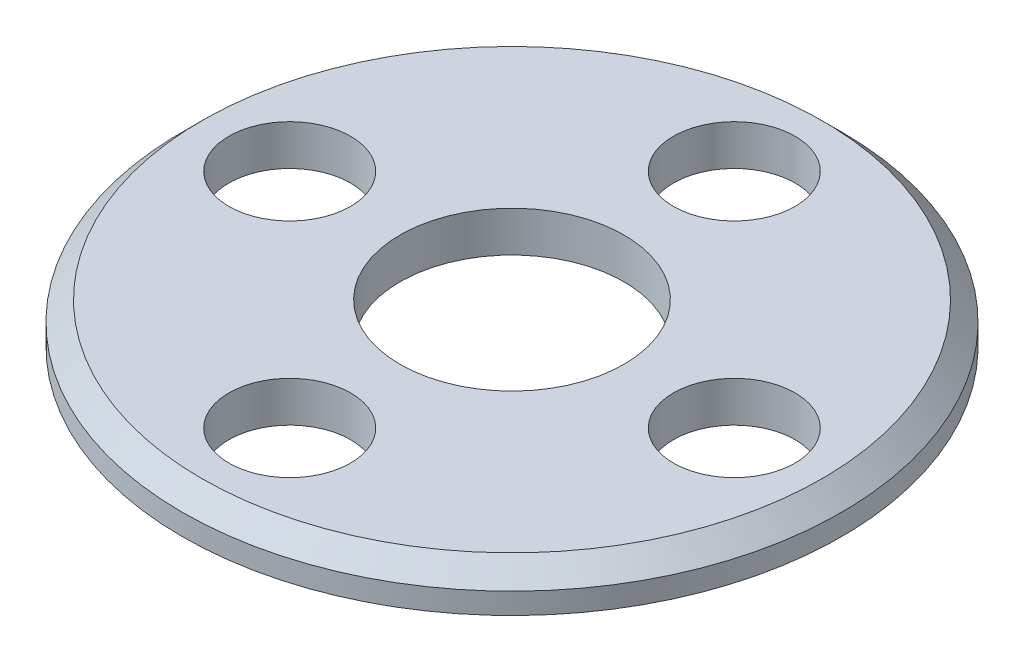
SolidWorks part; units mm, degrees
other "DetailItem2"
other "DetailItem3"
other "DetailItem4"
material "Alum Plate"
ref_plane "Front Plane" through (0, 0, 0) normal (0, 0, 1) x (1, 0, 0)
ref_plane "Top Plane" through (0, 0, 0) normal (0, 1, 0) x (1, 0, 0)
ref_plane "Right Plane" through (0, 0, 0) normal (1, 0, 0) x (0, 0, -1)
ref_axis "Centerline" through (0, 10.4775, 0) along (0, -1, 0)
sketch "Sketch1" plane through (0, 0, 0) normal (0, 1, 0) x (1, 0, 0)
  circle A0 centre (0, 0) radius 23.9697
  dimension "OuterDiameter" = 47.9394
extrude "ToothOD" add sketch "Sketch1" along normal mid plane 3.175
sketch "Sketch2" plane through (0, 1.5875, 0) normal (0, 1, 0) x (1, 0, 0)
  line L0 (0, 22.8013) -> (50000, 22.8013) construction
  line L1 (0, 23.9697) -> (50000, 23.9697) construction
  line L2 (0, 0) -> (0, 50000) construction
  arc A0 (-0.937, 23.5198) -> (0, 22.8013) centre (0, 23.7716) ccw
  arc A1 (-1.1386, 23.9426) -> (1.1386, 23.9426) centre (0, 0) cw
  circle A2 centre (0, 0) radius 23.9697 construction
  arc A3 (-0.937, 23.5198) -> (-1.0078, 23.7716) centre (-11.9754, 20.5533) ccw
  arc A4 (-1.0078, 23.7716) -> (-1.1386, 23.9426) centre (-1.2954, 23.6872) ccw
  circle A5 centre (0, 0) radius 23.9697 construction
  arc A6 (0.937, 23.5198) -> (1.0078, 23.7716) centre (11.9754, 20.5533) cw
  arc A7 (1.0078, 23.7716) -> (1.1386, 23.9426) centre (1.2954, 23.6872) cw
  arc A8 (0, 22.8013) -> (0.937, 23.5198) centre (0, 23.7716) ccw
  dimension "D1" = 1.9406
  dimension "D3" = 22.86
  dimension "D4" = 0.5994
  dimension "D2" = 1.1684
  dimension "D5" = 1.2954
extrude "ToothProfile" cut sketch "Sketch2" against normal through all
pattern_circular "ToothPattern" count 51 over 360 about axis through (0, 1.5875, 0) along (0, -1, 0) of "ToothProfile"
sketch "Sketch4" plane through (0, 0, 0) normal (0, 0, 1) x (1, 0, 0)
  line L0 (0, -5.08) -> (24.2237, -5.08)
  line L1 (0, -6.35) -> (25.7477, -6.35)
  line L2 (0, -6.35) -> (0, -5.08)
  line L3 (25.7477, -6.35) -> (25.7477, -5.842)
  line L4 (0, 0) -> (50000, 0) construction
  line L5 (25.7477, 6.35) -> (25.7477, 5.842)
  line L6 (0, 6.35) -> (0, 5.08)
  line L7 (0, 6.35) -> (25.7477, 6.35)
  line L8 (0, 5.08) -> (24.2237, 5.08)
  arc A0 (24.2237, -5.08) -> (24.6788, -5.1726) centre (23.944, -7.618) cw
  arc A2 (24.6788, -5.1726) -> (25.7477, -5.842) centre (23.5462, -8.1694) cw
  arc A3 (24.6788, 5.1726) -> (25.7477, 5.842) centre (23.5462, 8.1694) ccw
  arc A4 (24.2237, 5.08) -> (24.6788, 5.1726) centre (23.944, 7.618) ccw
  dimension "FlangeID" = 24.2237
  dimension "FlangeOD" = 25.7477
  dimension "D1" = 1.27
  dimension "D2" = 0.508
  dimension "D3" = 5.08
  dimension "D4" = 12.7
sketch "Sketch7" plane through (0, 0, 0) normal (0, -1, 0) x (1, 0, 0)
  line L1 (3.6662, 6.35) -> (-3.6662, 6.35)
  line L2 (-3.6662, 6.35) -> (-7.3323, 0)
  line L3 (-7.3323, 0) -> (-3.6662, -6.35)
  line L4 (-3.6662, -6.35) -> (3.6662, -6.35)
  line L5 (3.6662, -6.35) -> (7.3323, 0)
  line L6 (7.3323, 0) -> (3.6662, 6.35)
  circle A0 centre (0, 0) radius 6.35 construction
  dimension "HexBoreDi," = 12.7
extrude "Bore" [suppressed] cut sketch "Sketch7" against normal through all both and the other way through all
sketch "Sketch13" plane through (0, 1.5875, 0) normal (0, 1, 0) x (1, 0, 0)
  line L0 (-3.81, 20.2565) -> (3.81, 20.2565) construction
  line L4 (0, 20.2565) -> (0, 17.399) construction
  arc A0 (-3.81, 20.2565) -> (3.81, 20.2565) centre (0, 17.399) ccw
  circle A1 centre (0, 0) radius 8.7694
  arc A2 (3.81, 20.2565) -> (-3.81, 20.2565) centre (0, 17.399) ccw
  dimension "D1" = 9.525
  dimension "D3" = 17.5387
  dimension "D2" = 17.399
  dimension "D4" = 7.62
extrude "Cut-Extrude2" cut sketch "Sketch13" against normal through all
pattern_circular "CirPattern1" count 4 over 360 about axis through (0, -1.5875, 0) along (0, 1, 0) of "Cut-Extrude2"
sketch "Sketch14" plane through (0, 1.5875, 0) normal (0, 1, 0) x (1, 0, 0)
  circle A0 centre (0, 0) radius 22.733
  circle A1 centre (0, 0) radius 23.9697
  arc A3 (-3.2802, -23.7442) -> (-2.6104, -23.8271) centre (0, 0) ccw construction
  dimension "D1" = 45.466
extrude "Cut-Extrude3" [suppressed] cut sketch "Sketch14" against normal through all
sketch "Sketch15" plane through (0, 1.5875, 0) normal (0, 1, 0) x (1, 0, 0)
  circle A0 centre (0, 0) radius 25.7969
  arc A306 (6.9442, 22.9418) -> (6.7756, 22.8078) centre (7.0339, 22.6558) ccw
  arc A307 (6.7756, 22.8078) -> (6.6455, 22.5808) centre (16.6269, 17.0116) ccw
  arc A308 (4.8281, 23.038) -> (6.6455, 22.5808) centre (5.7982, 23.0536) ccw
  arc A309 (4.8281, 23.038) -> (4.8208, 23.2994) centre (-6.6004, 22.8535) ccw
  arc A310 (4.8208, 23.2994) -> (4.7357, 23.4972) centre (4.5214, 23.2877) ccw
  arc A311 (4.7357, 23.4972) -> (4.0723, 23.6213) centre (0, 0) ccw
  arc A312 (4.0723, 23.6213) -> (3.9214, 23.4676) centre (4.1965, 23.3485) ccw
  arc A313 (3.9214, 23.4676) -> (3.8202, 23.2264) centre (14.4104, 18.9259) ccw
  arc A314 (1.9604, 23.4567) -> (3.8202, 23.2264) centre (2.9212, 23.5914) ccw
  arc A315 (1.9604, 23.4567) -> (1.9211, 23.7153) centre (-9.3589, 21.8692) ccw
  arc A316 (1.9211, 23.7153) -> (1.8123, 23.9011) centre (1.6253, 23.6668) ccw
  arc A317 (1.8123, 23.9011) -> (1.1386, 23.9426) centre (0, 0) ccw
  arc A318 (1.1386, 23.9426) -> (1.0078, 23.7716) centre (1.2954, 23.6872) ccw
  arc A319 (1.0078, 23.7716) -> (0.937, 23.5198) centre (11.9754, 20.5533) ccw
  arc A320 (-0.937, 23.5198) -> (0.937, 23.5198) centre (0, 23.7716) ccw
  arc A321 (-0.937, 23.5198) -> (-1.0078, 23.7716) centre (-11.9754, 20.5533) ccw
  arc A322 (-1.0078, 23.7716) -> (-1.1386, 23.9426) centre (-1.2954, 23.6872) ccw
  arc A323 (-1.1386, 23.9426) -> (-1.8123, 23.9011) centre (0, 0) ccw
  arc A324 (-1.8123, 23.9011) -> (-1.9211, 23.7153) centre (-1.6253, 23.6668) ccw
  arc A325 (-1.9211, 23.7153) -> (-1.9604, 23.4567) centre (9.3589, 21.8692) ccw
  arc A326 (-3.8202, 23.2264) -> (-1.9604, 23.4567) centre (-2.9212, 23.5914) ccw
  arc A327 (-3.8202, 23.2264) -> (-3.9214, 23.4676) centre (-14.4104, 18.9259) ccw
  arc A328 (-3.9214, 23.4676) -> (-4.0723, 23.6213) centre (-4.1965, 23.3485) ccw
  arc A329 (-4.0723, 23.6213) -> (-4.7357, 23.4972) centre (0, 0) ccw
  arc A330 (-4.7357, 23.4972) -> (-4.8208, 23.2994) centre (-4.5214, 23.2877) ccw
  arc A331 (-4.8208, 23.2994) -> (-4.8281, 23.038) centre (6.6004, 22.8535) ccw
  arc A332 (-6.6455, 22.5808) -> (-4.8281, 23.038) centre (-5.7982, 23.0536) ccw
  arc A333 (-6.6455, 22.5808) -> (-6.7756, 22.8078) centre (-16.6269, 17.0116) ccw
  arc A334 (-6.7756, 22.8078) -> (-6.9442, 22.9418) centre (-7.0339, 22.6558) ccw
  arc A335 (-6.9442, 22.9418) -> (-7.5873, 22.7372) centre (0, 0) ccw
  arc A336 (-7.5873, 22.7372) -> (-7.6475, 22.5304) centre (-7.3489, 22.5556) ccw
  arc A337 (-7.6475, 22.5304) -> (-7.6226, 22.27) centre (3.742, 23.4914) ccw
  arc A338 (-9.3701, 21.593) -> (-7.6226, 22.27) centre (-8.5873, 22.1663) ccw
  arc A339 (-9.3701, 21.593) -> (-9.527, 21.8023) centre (-18.5914, 14.8394) ccw
  arc A340 (-9.527, 21.8023) -> (-9.7108, 21.9145) centre (-9.7647, 21.6197) ccw
  arc A341 (-9.7108, 21.9145) -> (-10.324, 21.6324) centre (0, 0) ccw
  arc A342 (-10.324, 21.6324) -> (-10.3583, 21.4198) centre (-10.065, 21.4816) ccw
  arc A343 (-10.3583, 21.4198) -> (-10.3015, 21.1645) centre (0.8268, 23.7732) ccw
  arc A344 (-11.9526, 20.2779) -> (-10.3015, 21.1645) centre (-11.2462, 20.9431) ccw
  arc A345 (-11.9526, 20.2779) -> (-12.1341, 20.4663) centre (-20.2741, 12.4423) ccw
  arc A346 (-12.1341, 20.4663) -> (-12.3303, 20.5551) centre (-12.3475, 20.2559) ccw
  arc A347 (-12.3303, 20.5551) -> (-12.9041, 20.1998) centre (0, 0) ccw
  arc A348 (-12.9041, 20.1998) -> (-12.912, 19.9846) centre (-12.6285, 20.0819) ccw
  arc A349 (-12.912, 19.9846) -> (-12.8243, 19.7382) centre (-2.1009, 23.6946) ccw
  arc A350 (-14.3539, 18.6554) -> (-12.8243, 19.7382) centre (-13.7346, 19.4023) ccw
  arc A351 (-14.3539, 18.6554) -> (-14.5572, 18.82) centre (-21.6494, 9.8565) ccw
  arc A352 (-14.5572, 18.82) -> (-14.7628, 18.884) centre (-14.7431, 18.585) ccw
  arc A353 (-14.7628, 18.884) -> (-15.2886, 18.4609) centre (0, 0) ccw
  arc A354 (-15.2886, 18.4609) -> (-15.27, 18.2464) centre (-15.0006, 18.3778) ccw
  arc A355 (-15.27, 18.2464) -> (-15.1527, 18.0126) centre (-4.9968, 23.2569) ccw
  arc A356 (-16.5376, 16.75) -> (-15.1527, 18.0126) centre (-16.0148, 17.5674) ccw
  arc A357 (-16.5376, 16.75) -> (-16.7596, 16.8885) centre (-22.6966, 7.1213) ccw
  arc A358 (-16.7596, 16.8885) -> (-16.9715, 16.9267) centre (-16.9153, 16.6323) ccw
  arc A359 (-16.9715, 16.9267) -> (-17.4414, 16.4422) centre (0, 0) ccw
  arc A360 (-17.4414, 16.4422) -> (-17.3966, 16.2316) centre (-17.1454, 16.3951) ccw
  arc A361 (-17.3966, 16.2316) -> (-17.2514, 16.014) centre (-7.8169, 22.4665) ccw
  arc A362 (-18.4707, 14.5908) -> (-17.2514, 16.014) centre (-18.0523, 15.4662) ccw
  arc A363 (-18.4707, 14.5908) -> (-18.708, 14.7009) centre (-23.3997, 4.2782) ccw
  arc A364 (-18.708, 14.7009) -> (-18.923, 14.7128) centre (-18.831, 14.4276) ccw
  arc A365 (-18.923, 14.7128) -> (-19.3297, 14.1742) centre (0, 0) ccw
  arc A366 (-19.3297, 14.1742) -> (-19.2594, 13.9707) centre (-19.0302, 14.1638) ccw
  arc A367 (-19.2594, 13.9707) -> (-19.0886, 13.7726) centre (-10.5185, 21.3356) ccw
  arc A368 (-20.1237, 12.2104) -> (-19.0886, 13.7726) centre (-19.8161, 13.1306) ccw
  arc A369 (-20.1237, 12.2104) -> (-20.3727, 12.2905) centre (-23.7481, 1.3702) ccw
  arc A370 (-20.3727, 12.2905) -> (-20.5876, 12.2759) centre (-20.4612, 12.0041) ccw
  arc A371 (-20.5876, 12.2759) -> (-20.925, 11.6914) centre (0, 0) ccw
  arc A372 (-20.925, 11.6914) -> (-20.8302, 11.4981) centre (-20.6265, 11.7179) ccw
  arc A373 (-20.8302, 11.4981) -> (-20.6364, 11.3225) centre (-13.0607, 19.8813) ccw
  arc A374 (-21.4717, 9.6449) -> (-20.6364, 11.3225) centre (-21.2795, 10.5959) ccw
  arc A375 (-21.4717, 9.6449) -> (-21.7287, 9.6938) centre (-23.7365, -1.5585) ccw
  arc A376 (-21.7287, 9.6938) -> (-21.9401, 9.6529) centre (-21.7813, 9.3987) ccw
  arc A377 (-21.9401, 9.6529) -> (-22.2032, 9.0314) centre (0, 0) ccw
  arc A378 (-22.2032, 9.0314) -> (-22.0853, 8.8511) centre (-21.9102, 9.0943) ccw
  arc A379 (-22.0853, 8.8511) -> (-21.8713, 8.7007) centre (-15.4049, 18.1256) ccw
  arc A380 (-22.4942, 6.9331) -> (-21.8713, 8.7007) centre (-22.4203, 7.9006) ccw
  arc A381 (-22.4942, 6.9331) -> (-22.7552, 6.9501) centre (-23.365, -4.4636) ccw
  arc A382 (-22.7552, 6.9501) -> (-22.96, 6.8836) centre (-22.7712, 6.6508) ccw
  arc A383 (-22.96, 6.8836) -> (-23.1447, 6.2344) centre (0, 0) ccw
  arc A384 (-23.1447, 6.2344) -> (-23.0056, 6.07) centre (-22.8617, 6.3329) ccw
  arc A385 (-23.0056, 6.07) -> (-22.7748, 5.947) centre (-17.5156, 16.0952) ccw
  arc A386 (-23.1757, 4.1163) -> (-22.7748, 5.947) centre (-23.2212, 5.0855) ccw
  arc A387 (-23.1757, 4.1163) -> (-23.4368, 4.1011) centre (-22.6394, -7.3011) ccw
  arc A388 (-23.4368, 4.1011) -> (-23.6319, 4.0099) centre (-23.4159, 3.8021) ccw
  arc A389 (-23.6319, 4.0099) -> (-23.7355, 3.3429) centre (0, 0) ccw
  arc A390 (-23.7355, 3.3429) -> (-23.5772, 3.1969) centre (-23.4666, 3.4755) ccw
  arc A391 (-23.5772, 3.1969) -> (-23.333, 3.1032) centre (-19.3607, 13.8207) ccw
  arc A392 (-23.5059, 1.2371) -> (-23.333, 3.1032) centre (-23.6702, 2.1934) ccw
  arc A393 (-23.5059, 1.2371) -> (-23.7632, 1.1899) centre (-21.5706, -10.0279) ccw
  arc A394 (-23.7632, 1.1899) -> (-23.9456, 1.0754) centre (-23.7057, 0.8957) ccw
  arc A395 (-23.9456, 1.0754) -> (-23.9664, 0.4008) centre (0, 0) ccw
  arc A396 (-23.9664, 0.4008) -> (-23.7913, 0.2753) centre (-23.7159, 0.5653) ccw
  arc A397 (-23.7913, 0.2753) -> (-23.5375, 0.2123) centre (-20.9124, 11.3368) ccw
  arc A398 (-23.4798, -1.6609) -> (-23.5375, 0.2123) centre (-23.7603, -0.732) ccw
  arc A399 (-23.4798, -1.6609) -> (-23.7293, -1.7394) centre (-20.1748, -12.6026) ccw
  arc A400 (-23.7293, -1.7394) -> (-23.8962, -1.8754) centre (-23.6361, -2.0242) ccw
  arc A401 (-23.8962, -1.8754) -> (-23.834, -2.5474) centre (0, 0) ccw
  arc A402 (-23.834, -2.5474) -> (-23.6449, -2.6505) centre (-23.6056, -2.3533) ccw
  arc A403 (-23.6449, -2.6505) -> (-23.3852, -2.6818) centre (-22.147, 8.6809) ccw
  arc A404 (-23.0977, -4.5337) -> (-23.3852, -2.6818) centre (-23.4903, -3.6464) ccw
  arc A405 (-23.0977, -4.5337) -> (-23.3357, -4.6422) centre (-18.4732, -14.9864) ccw
  arc A406 (-23.3357, -4.6422) -> (-23.4846, -4.7978) centre (-23.2082, -4.9135) ccw
  arc A407 (-23.4846, -4.7978) -> (-23.3403, -5.4571) centre (0, 0) ccw
  arc A408 (-23.3403, -5.4571) -> (-23.1399, -5.5361) centre (-23.1375, -5.2364) ccw
  arc A409 (-23.1399, -5.5361) -> (-22.8783, -5.5352) centre (-23.0459, 5.8935) ccw
  arc A410 (-22.3655, -7.3378) -> (-22.8783, -5.5352) centre (-22.8641, -6.5054) ccw
  arc A411 (-22.3655, -7.3378) -> (-22.5883, -7.4747) centre (-16.4915, -17.1429) ccw
  arc A412 (-22.5883, -7.4747) -> (-22.7171, -7.6474) centre (-22.4285, -7.7283) ccw
  arc A413 (-22.7171, -7.6474) -> (-22.4927, -8.2839) centre (0, 0) ccw
  arc A414 (-22.4927, -8.2839) -> (-22.2842, -8.3377) centre (-22.3186, -8.04) ccw
  arc A415 (-22.2842, -8.3377) -> (-22.0247, -8.3048) centre (-23.5955, 3.0168) ccw
  arc A416 (-21.2942, -10.0306) -> (-22.0247, -8.3048) centre (-21.8914, -9.2658) ccw
  arc A417 (-21.2942, -10.0306) -> (-21.4986, -10.1939) centre (-14.2598, -19.0396) ccw
  arc A418 (-21.4986, -10.1939) -> (-21.6051, -10.3811) centre (-21.3087, -10.4259) ccw
  arc A419 (-21.6051, -10.3811) -> (-21.3043, -10.9852) centre (0, 0) ccw
  arc A420 (-21.3043, -10.9852) -> (-21.0907, -11.013) centre (-21.1614, -10.7217) ccw
  arc A421 (-21.0907, -11.013) -> (-20.8372, -10.9484) centre (-23.7874, 0.0943) ccw
  arc A422 (-19.9002, -12.5714) -> (-20.8372, -10.9484) centre (-20.5868, -11.8858) ccw
  arc A423 (-19.9002, -12.5714) -> (-20.0829, -12.7586) centre (-11.812, -20.6476) ccw
  arc A424 (-20.0829, -12.7586) -> (-20.1656, -12.9574) centre (-19.866, -12.9654) ccw
  arc A425 (-20.1656, -12.9574) -> (-19.7928, -13.52) centre (0, 0) ccw
  arc A426 (-19.7928, -13.52) -> (-19.5775, -13.5213) centre (-19.6834, -13.241) ccw
  arc A427 (-19.5775, -13.5213) -> (-19.3339, -13.4261) centre (-23.6187, -2.8296) ccw
  arc A428 (-18.2045, -14.9216) -> (-19.3339, -13.4261) centre (-18.9701, -14.3256) ccw
  arc A429 (-18.2045, -14.9216) -> (-18.3628, -15.1298) centre (-9.1851, -21.9427) ccw
  arc A430 (-18.3628, -15.1298) -> (-18.4205, -15.3373) centre (-18.1221, -15.3085) ccw
  arc A431 (-18.4205, -15.3373) -> (-17.9814, -15.8499) centre (0, 0) ccw
  arc A432 (-17.9814, -15.8499) -> (-17.7675, -15.8247) centre (-17.9071, -15.5595) ccw
  arc A433 (-17.7675, -15.8247) -> (-17.5374, -15.7002) centre (-23.0919, -5.7106) ccw
  arc A434 (-16.2328, -17.0456) -> (-17.5374, -15.7002) centre (-17.0659, -16.5482) ccw
  arc A435 (-16.2328, -17.0456) -> (-16.3643, -17.2717) centre (-6.419, -22.9051) ccw
  arc A436 (-16.3643, -17.2717) -> (-16.3961, -17.4847) centre (-16.1035, -17.4194) ccw
  arc A437 (-16.3961, -17.4847) -> (-15.8973, -17.9394) centre (0, 0) ccw
  arc A438 (-15.8973, -17.9394) -> (-15.6881, -17.8882) centre (-15.8593, -17.6421) ccw
  arc A439 (-15.6881, -17.8882) -> (-15.4751, -17.7363) centre (-22.2152, -8.505) ccw
  arc A440 (-14.0151, -18.9112) -> (-15.4751, -17.7363) centre (-14.903, -18.52) ccw
  arc A441 (-14.0151, -18.9112) -> (-14.1178, -19.1518) centre (-3.5556, -23.5203) ccw
  arc A442 (-14.1178, -19.1518) -> (-14.1231, -19.3671) centre (-13.8408, -19.2664) ccw
  arc A443 (-14.1231, -19.3671) -> (-13.5723, -19.757) centre (0, 0) ccw
  arc A444 (-13.5723, -19.757) -> (-13.371, -19.6805) centre (-13.5711, -19.4573) ccw
  arc A445 (-13.371, -19.6805) -> (-13.1782, -19.5036) centre (-21.0016, -11.1706) ccw
  arc A446 (-11.5849, -20.4902) -> (-13.1782, -19.5036) centre (-12.5141, -20.211) ccw
  arc A447 (-11.5849, -20.4902) -> (-11.6573, -20.7416) centre (-0.6383, -23.779) ccw
  arc A448 (-11.6573, -20.7416) -> (-11.6361, -20.9559) centre (-11.3683, -20.8212) ccw
  arc A449 (-11.6361, -20.9559) -> (-11.0415, -21.2752) centre (0, 0) ccw
  arc A450 (-11.0415, -21.2752) -> (-10.8511, -21.1744) centre (-11.0771, -20.9776) ccw
  arc A451 (-10.8511, -21.1744) -> (-10.6816, -20.9753) centre (-19.4697, -13.6667) ccw
  arc A452 (-8.9791, -21.7585) -> (-10.6816, -20.9753) centre (-9.9356, -21.5957) ccw
  arc A453 (-8.9791, -21.7585) -> (-9.02, -22.0169) centre (2.2887, -23.6772) ccw
  arc A454 (-9.02, -22.0169) -> (-8.9727, -22.227) centre (-8.7235, -22.0604) ccw
  arc A455 (-8.9727, -22.227) -> (-8.3433, -22.4708) centre (0, 0) ccw
  arc A456 (-8.3433, -22.4708) -> (-8.1668, -22.3474) centre (-8.4153, -22.1798) ccw
  arc A457 (-8.1668, -22.3474) -> (-8.023, -22.1289) centre (-17.6426, -15.9558) ccw
  arc A458 (-6.2371, -22.697) -> (-8.023, -22.1289) centre (-7.2064, -22.6529) ccw
  arc A459 (-6.2371, -22.697) -> (-6.246, -22.9585) centre (5.181, -23.2165) ccw
  arc A460 (-6.246, -22.9585) -> (-6.1732, -23.1611) centre (-5.9464, -22.9652) ccw
  arc A461 (-6.1732, -23.1611) -> (-5.5187, -23.3258) centre (0, 0) ccw
  arc A462 (-5.5187, -23.3258) -> (-5.3587, -23.1816) centre (-5.6259, -23.0458) ccw
  arc A463 (-5.3587, -23.1816) -> (-5.2428, -22.9471) centre (-15.5481, -18.0029) ccw
  arc A464 (-3.4007, -23.2915) -> (-5.2428, -22.9471) centre (-4.368, -23.3668) ccw
  arc A465 (-3.4007, -23.2915) -> (-3.3774, -23.552) centre (7.9948, -22.4038) ccw
  arc A466 (-3.3774, -23.552) -> (-3.2802, -23.7442) centre (-3.0792, -23.5219) ccw
  arc A467 (-3.2802, -23.7442) -> (-2.6104, -23.8271) centre (0, 0) ccw
  arc A468 (-2.6104, -23.8271) -> (-2.4693, -23.6645) centre (-2.7511, -23.5625) ccw
  arc A469 (-2.4693, -23.6645) -> (-2.3832, -23.4175) centre (-13.2179, -19.7771) ccw
  arc A470 (-0.5126, -23.5328) -> (-2.3832, -23.4175) centre (-1.4634, -23.7265) ccw
  arc A471 (-0.5126, -23.5328) -> (-0.4575, -23.7885) centre (10.6874, -21.2516) ccw
  arc A472 (-0.4575, -23.7885) -> (-0.3375, -23.9673) centre (-0.1653, -23.722) ccw
  arc A473 (-0.3375, -23.9673) -> (0.3375, -23.9673) centre (0, 0) ccw
  arc A474 (0.3375, -23.9673) -> (0.4575, -23.7885) centre (0.1653, -23.722) ccw
  arc A475 (0.4575, -23.7885) -> (0.5126, -23.5328) centre (-10.6874, -21.2516) ccw
  arc A476 (2.3832, -23.4175) -> (0.5126, -23.5328) centre (1.4634, -23.7265) ccw
  arc A477 (2.3832, -23.4175) -> (2.4693, -23.6645) centre (13.2179, -19.7771) ccw
  arc A478 (2.4693, -23.6645) -> (2.6104, -23.8271) centre (2.7511, -23.5625) ccw
  arc A479 (2.6104, -23.8271) -> (3.2802, -23.7442) centre (0, 0) ccw
  arc A480 (3.2802, -23.7442) -> (3.3774, -23.552) centre (3.0792, -23.5219) ccw
  arc A481 (3.3774, -23.552) -> (3.4007, -23.2915) centre (-7.9948, -22.4038) ccw
  arc A482 (5.2428, -22.9471) -> (3.4007, -23.2915) centre (4.368, -23.3668) ccw
  arc A483 (5.2428, -22.9471) -> (5.3587, -23.1816) centre (15.5481, -18.0029) ccw
  arc A484 (5.3587, -23.1816) -> (5.5187, -23.3258) centre (5.6259, -23.0458) ccw
  arc A485 (5.5187, -23.3258) -> (6.1732, -23.1611) centre (0, 0) ccw
  arc A486 (6.1732, -23.1611) -> (6.246, -22.9585) centre (5.9464, -22.9652) ccw
  arc A487 (6.246, -22.9585) -> (6.2371, -22.697) centre (-5.181, -23.2165) ccw
  arc A488 (8.023, -22.1289) -> (6.2371, -22.697) centre (7.2064, -22.6529) ccw
  arc A489 (8.023, -22.1289) -> (8.1668, -22.3474) centre (17.6426, -15.9558) ccw
  arc A490 (8.1668, -22.3474) -> (8.3433, -22.4708) centre (8.4153, -22.1798) ccw
  arc A491 (8.3433, -22.4708) -> (8.9727, -22.227) centre (0, 0) ccw
  arc A492 (8.9727, -22.227) -> (9.02, -22.0169) centre (8.7235, -22.0604) ccw
  arc A493 (9.02, -22.0169) -> (8.9791, -21.7585) centre (-2.2887, -23.6772) ccw
  arc A494 (10.6816, -20.9753) -> (8.9791, -21.7585) centre (9.9356, -21.5957) ccw
  arc A495 (10.6816, -20.9753) -> (10.8511, -21.1744) centre (19.4697, -13.6667) ccw
  arc A496 (10.8511, -21.1744) -> (11.0415, -21.2752) centre (11.0771, -20.9776) ccw
  arc A497 (11.0415, -21.2752) -> (11.6361, -20.9559) centre (0, 0) ccw
  arc A498 (11.6361, -20.9559) -> (11.6573, -20.7416) centre (11.3683, -20.8212) ccw
  arc A499 (11.6573, -20.7416) -> (11.5849, -20.4902) centre (0.6383, -23.779) ccw
  arc A500 (13.1782, -19.5036) -> (11.5849, -20.4902) centre (12.5141, -20.211) ccw
  arc A501 (13.1782, -19.5036) -> (13.371, -19.6805) centre (21.0016, -11.1706) ccw
  arc A502 (13.371, -19.6805) -> (13.5723, -19.757) centre (13.5711, -19.4573) ccw
  arc A503 (13.5723, -19.757) -> (14.1231, -19.3671) centre (0, 0) ccw
  arc A504 (14.1231, -19.3671) -> (14.1178, -19.1518) centre (13.8408, -19.2664) ccw
  arc A505 (14.1178, -19.1518) -> (14.0151, -18.9112) centre (3.5556, -23.5203) ccw
  arc A506 (15.4751, -17.7363) -> (14.0151, -18.9112) centre (14.903, -18.52) ccw
  arc A507 (15.4751, -17.7363) -> (15.6881, -17.8882) centre (22.2152, -8.505) ccw
  arc A508 (15.6881, -17.8882) -> (15.8973, -17.9394) centre (15.8593, -17.6421) ccw
  arc A509 (15.8973, -17.9394) -> (16.3961, -17.4847) centre (0, 0) ccw
  arc A510 (16.3961, -17.4847) -> (16.3643, -17.2717) centre (16.1035, -17.4194) ccw
  arc A511 (16.3643, -17.2717) -> (16.2328, -17.0456) centre (6.419, -22.9051) ccw
  arc A512 (17.5374, -15.7002) -> (16.2328, -17.0456) centre (17.0659, -16.5482) ccw
  arc A513 (17.5374, -15.7002) -> (17.7675, -15.8247) centre (23.0919, -5.7106) ccw
  arc A514 (17.7675, -15.8247) -> (17.9814, -15.8499) centre (17.9071, -15.5595) ccw
  arc A515 (17.9814, -15.8499) -> (18.4205, -15.3373) centre (0, 0) ccw
  arc A516 (18.4205, -15.3373) -> (18.3628, -15.1298) centre (18.1221, -15.3085) ccw
  arc A517 (18.3628, -15.1298) -> (18.2045, -14.9216) centre (9.1851, -21.9427) ccw
  arc A518 (19.3339, -13.4261) -> (18.2045, -14.9216) centre (18.9701, -14.3256) ccw
  arc A519 (19.3339, -13.4261) -> (19.5775, -13.5213) centre (23.6187, -2.8296) ccw
  arc A520 (19.5775, -13.5213) -> (19.7928, -13.52) centre (19.6834, -13.241) ccw
  arc A521 (19.7928, -13.52) -> (20.1656, -12.9574) centre (0, 0) ccw
  arc A522 (20.1656, -12.9574) -> (20.0829, -12.7586) centre (19.866, -12.9654) ccw
  arc A523 (20.0829, -12.7586) -> (19.9002, -12.5714) centre (11.812, -20.6476) ccw
  arc A524 (20.8372, -10.9484) -> (19.9002, -12.5714) centre (20.5868, -11.8858) ccw
  arc A525 (20.8372, -10.9484) -> (21.0907, -11.013) centre (23.7874, 0.0943) ccw
  arc A526 (21.0907, -11.013) -> (21.3043, -10.9852) centre (21.1614, -10.7217) ccw
  arc A527 (21.3043, -10.9852) -> (21.6051, -10.3811) centre (0, 0) ccw
  arc A528 (21.6051, -10.3811) -> (21.4986, -10.1939) centre (21.3087, -10.4259) ccw
  arc A529 (21.4986, -10.1939) -> (21.2942, -10.0306) centre (14.2598, -19.0396) ccw
  arc A530 (22.0247, -8.3048) -> (21.2942, -10.0306) centre (21.8914, -9.2658) ccw
  arc A531 (22.0247, -8.3048) -> (22.2842, -8.3377) centre (23.5955, 3.0168) ccw
  arc A532 (22.2842, -8.3377) -> (22.4927, -8.2839) centre (22.3186, -8.04) ccw
  arc A533 (22.4927, -8.2839) -> (22.7171, -7.6474) centre (0, 0) ccw
  arc A534 (22.7171, -7.6474) -> (22.5883, -7.4747) centre (22.4285, -7.7283) ccw
  arc A535 (22.5883, -7.4747) -> (22.3655, -7.3378) centre (16.4915, -17.1429) ccw
  arc A536 (22.8783, -5.5352) -> (22.3655, -7.3378) centre (22.8641, -6.5054) ccw
  arc A537 (22.8783, -5.5352) -> (23.1399, -5.5361) centre (23.0459, 5.8935) ccw
  arc A538 (23.1399, -5.5361) -> (23.3403, -5.4571) centre (23.1375, -5.2364) ccw
  arc A539 (23.3403, -5.4571) -> (23.4846, -4.7978) centre (0, 0) ccw
  arc A540 (23.4846, -4.7978) -> (23.3357, -4.6422) centre (23.2082, -4.9135) ccw
  arc A541 (23.3357, -4.6422) -> (23.0977, -4.5337) centre (18.4732, -14.9864) ccw
  arc A542 (23.3852, -2.6818) -> (23.0977, -4.5337) centre (23.4903, -3.6464) ccw
  arc A543 (23.3852, -2.6818) -> (23.6449, -2.6505) centre (22.147, 8.6809) ccw
  arc A544 (23.6449, -2.6505) -> (23.834, -2.5474) centre (23.6056, -2.3533) ccw
  arc A545 (23.834, -2.5474) -> (23.8962, -1.8754) centre (0, 0) ccw
  arc A546 (23.8962, -1.8754) -> (23.7293, -1.7394) centre (23.6361, -2.0242) ccw
  arc A547 (23.7293, -1.7394) -> (23.4798, -1.6609) centre (20.1748, -12.6026) ccw
  arc A548 (23.5375, 0.2123) -> (23.4798, -1.6609) centre (23.7603, -0.732) ccw
  arc A549 (23.5375, 0.2123) -> (23.7913, 0.2753) centre (20.9124, 11.3368) ccw
  arc A550 (23.7913, 0.2753) -> (23.9664, 0.4008) centre (23.7159, 0.5653) ccw
  arc A551 (23.9664, 0.4008) -> (23.9456, 1.0754) centre (0, 0) ccw
  arc A552 (23.9456, 1.0754) -> (23.7632, 1.1899) centre (23.7057, 0.8957) ccw
  arc A553 (23.7632, 1.1899) -> (23.5059, 1.2371) centre (21.5706, -10.0279) ccw
  arc A554 (23.333, 3.1032) -> (23.5059, 1.2371) centre (23.6702, 2.1934) ccw
  arc A555 (23.333, 3.1032) -> (23.5772, 3.1969) centre (19.3607, 13.8207) ccw
  arc A556 (23.5772, 3.1969) -> (23.7355, 3.3429) centre (23.4666, 3.4755) ccw
  arc A557 (23.7355, 3.3429) -> (23.6319, 4.0099) centre (0, 0) ccw
  arc A558 (23.6319, 4.0099) -> (23.4368, 4.1011) centre (23.4159, 3.8021) ccw
  arc A559 (23.4368, 4.1011) -> (23.1757, 4.1163) centre (22.6394, -7.3011) ccw
  arc A560 (22.7748, 5.947) -> (23.1757, 4.1163) centre (23.2212, 5.0855) ccw
  arc A561 (22.7748, 5.947) -> (23.0056, 6.07) centre (17.5156, 16.0952) ccw
  arc A562 (23.0056, 6.07) -> (23.1447, 6.2344) centre (22.8617, 6.3329) ccw
  arc A563 (23.1447, 6.2344) -> (22.96, 6.8836) centre (0, 0) ccw
  arc A564 (22.96, 6.8836) -> (22.7552, 6.9501) centre (22.7712, 6.6508) ccw
  arc A565 (22.7552, 6.9501) -> (22.4942, 6.9331) centre (23.365, -4.4636) ccw
  arc A566 (21.8713, 8.7007) -> (22.4942, 6.9331) centre (22.4203, 7.9006) ccw
  arc A567 (21.8713, 8.7007) -> (22.0853, 8.8511) centre (15.4049, 18.1256) ccw
  arc A568 (22.0853, 8.8511) -> (22.2032, 9.0314) centre (21.9102, 9.0943) ccw
  arc A569 (22.2032, 9.0314) -> (21.9401, 9.6529) centre (0, 0) ccw
  arc A570 (21.9401, 9.6529) -> (21.7287, 9.6938) centre (21.7813, 9.3987) ccw
  arc A571 (21.7287, 9.6938) -> (21.4717, 9.6449) centre (23.7365, -1.5585) ccw
  arc A572 (20.6364, 11.3225) -> (21.4717, 9.6449) centre (21.2795, 10.5959) ccw
  arc A573 (20.6364, 11.3225) -> (20.8302, 11.4981) centre (13.0607, 19.8813) ccw
  arc A574 (20.8302, 11.4981) -> (20.925, 11.6914) centre (20.6265, 11.7179) ccw
  arc A575 (20.925, 11.6914) -> (20.5876, 12.2759) centre (0, 0) ccw
  arc A576 (20.5876, 12.2759) -> (20.3727, 12.2905) centre (20.4612, 12.0041) ccw
  arc A577 (20.3727, 12.2905) -> (20.1237, 12.2104) centre (23.7481, 1.3702) ccw
  arc A578 (19.0886, 13.7726) -> (20.1237, 12.2104) centre (19.8161, 13.1306) ccw
  arc A579 (19.0886, 13.7726) -> (19.2594, 13.9707) centre (10.5185, 21.3356) ccw
  arc A580 (19.2594, 13.9707) -> (19.3297, 14.1742) centre (19.0302, 14.1638) ccw
  arc A581 (19.3297, 14.1742) -> (18.923, 14.7128) centre (0, 0) ccw
  arc A582 (18.923, 14.7128) -> (18.708, 14.7009) centre (18.831, 14.4276) ccw
  arc A583 (18.708, 14.7009) -> (18.4707, 14.5908) centre (23.3997, 4.2782) ccw
  arc A584 (17.2514, 16.014) -> (18.4707, 14.5908) centre (18.0523, 15.4662) ccw
  arc A585 (17.2514, 16.014) -> (17.3966, 16.2316) centre (7.8169, 22.4665) ccw
  arc A586 (17.3966, 16.2316) -> (17.4414, 16.4422) centre (17.1454, 16.3951) ccw
  arc A587 (17.4414, 16.4422) -> (16.9715, 16.9267) centre (0, 0) ccw
  arc A588 (16.9715, 16.9267) -> (16.7596, 16.8885) centre (16.9153, 16.6323) ccw
  arc A589 (16.7596, 16.8885) -> (16.5376, 16.75) centre (22.6966, 7.1213) ccw
  arc A590 (15.1527, 18.0126) -> (16.5376, 16.75) centre (16.0148, 17.5674) ccw
  arc A591 (15.1527, 18.0126) -> (15.27, 18.2464) centre (4.9968, 23.2569) ccw
  arc A592 (15.27, 18.2464) -> (15.2886, 18.4609) centre (15.0006, 18.3778) ccw
  arc A593 (15.2886, 18.4609) -> (14.7628, 18.884) centre (0, 0) ccw
  arc A594 (14.7628, 18.884) -> (14.5572, 18.82) centre (14.7431, 18.585) ccw
  arc A595 (14.5572, 18.82) -> (14.3539, 18.6554) centre (21.6494, 9.8565) ccw
  arc A596 (12.8243, 19.7382) -> (14.3539, 18.6554) centre (13.7346, 19.4023) ccw
  arc A597 (12.8243, 19.7382) -> (12.912, 19.9846) centre (2.1009, 23.6946) ccw
  arc A598 (12.912, 19.9846) -> (12.9041, 20.1998) centre (12.6285, 20.0819) ccw
  arc A599 (12.9041, 20.1998) -> (12.3303, 20.5551) centre (0, 0) ccw
  arc A600 (12.3303, 20.5551) -> (12.1341, 20.4663) centre (12.3475, 20.2559) ccw
  arc A601 (12.1341, 20.4663) -> (11.9526, 20.2779) centre (20.2741, 12.4423) ccw
  arc A602 (10.3015, 21.1645) -> (11.9526, 20.2779) centre (11.2462, 20.9431) ccw
  arc A603 (10.3015, 21.1645) -> (10.3583, 21.4198) centre (-0.8268, 23.7732) ccw
  arc A604 (10.3583, 21.4198) -> (10.324, 21.6324) centre (10.065, 21.4816) ccw
  arc A605 (10.324, 21.6324) -> (9.7108, 21.9145) centre (0, 0) ccw
  arc A606 (9.7108, 21.9145) -> (9.527, 21.8023) centre (9.7647, 21.6197) ccw
  arc A607 (9.527, 21.8023) -> (9.3701, 21.593) centre (18.5914, 14.8394) ccw
  arc A608 (7.6226, 22.27) -> (9.3701, 21.593) centre (8.5873, 22.1663) ccw
  arc A609 (7.6226, 22.27) -> (7.6475, 22.5304) centre (-3.742, 23.4914) ccw
  arc A610 (7.6475, 22.5304) -> (7.5873, 22.7372) centre (7.3489, 22.5556) ccw
  arc A611 (7.5873, 22.7372) -> (6.9442, 22.9418) centre (0, 0) ccw
  arc A612 (6.9442, 22.9418) -> (6.7756, 22.8078) centre (7.0339, 22.6558) ccw
  arc A613 (6.7756, 22.8078) -> (6.6455, 22.5808) centre (16.6269, 17.0116) ccw
  arc A614 (4.8281, 23.038) -> (6.6455, 22.5808) centre (5.7982, 23.0536) ccw
  arc A615 (4.8281, 23.038) -> (4.8208, 23.2994) centre (-6.6004, 22.8535) ccw
  arc A616 (4.8208, 23.2994) -> (4.7357, 23.4972) centre (4.5214, 23.2877) ccw
  arc A617 (4.7357, 23.4972) -> (4.0723, 23.6213) centre (0, 0) ccw
  arc A618 (4.0723, 23.6213) -> (3.9214, 23.4676) centre (4.1965, 23.3485) ccw
  arc A619 (3.9214, 23.4676) -> (3.8202, 23.2264) centre (14.4104, 18.9259) ccw
  arc A620 (1.9604, 23.4567) -> (3.8202, 23.2264) centre (2.9212, 23.5914) ccw
  arc A621 (1.9604, 23.4567) -> (1.9211, 23.7153) centre (-9.3589, 21.8692) ccw
  arc A622 (1.9211, 23.7153) -> (1.8123, 23.9011) centre (1.6253, 23.6668) ccw
  arc A623 (1.8123, 23.9011) -> (1.1386, 23.9426) centre (0, 0) ccw
  arc A624 (1.1386, 23.9426) -> (1.0078, 23.7716) centre (1.2954, 23.6872) ccw
  arc A625 (1.0078, 23.7716) -> (0.937, 23.5198) centre (11.9754, 20.5533) ccw
  arc A626 (-0.937, 23.5198) -> (0.937, 23.5198) centre (0, 23.7716) ccw
  arc A627 (-0.937, 23.5198) -> (-1.0078, 23.7716) centre (-11.9754, 20.5533) ccw
  arc A628 (-1.0078, 23.7716) -> (-1.1386, 23.9426) centre (-1.2954, 23.6872) ccw
  arc A629 (-1.1386, 23.9426) -> (-1.8123, 23.9011) centre (0, 0) ccw
  arc A630 (-1.8123, 23.9011) -> (-1.9211, 23.7153) centre (-1.6253, 23.6668) ccw
  arc A631 (-1.9211, 23.7153) -> (-1.9604, 23.4567) centre (9.3589, 21.8692) ccw
  arc A632 (-3.8202, 23.2264) -> (-1.9604, 23.4567) centre (-2.9212, 23.5914) ccw
  arc A633 (-3.8202, 23.2264) -> (-3.9214, 23.4676) centre (-14.4104, 18.9259) ccw
  arc A634 (-3.9214, 23.4676) -> (-4.0723, 23.6213) centre (-4.1965, 23.3485) ccw
  arc A635 (-4.0723, 23.6213) -> (-4.7357, 23.4972) centre (0, 0) ccw
  arc A636 (-4.7357, 23.4972) -> (-4.8208, 23.2994) centre (-4.5214, 23.2877) ccw
  arc A637 (-4.8208, 23.2994) -> (-4.8281, 23.038) centre (6.6004, 22.8535) ccw
  arc A638 (-6.6455, 22.5808) -> (-4.8281, 23.038) centre (-5.7982, 23.0536) ccw
  arc A639 (-6.6455, 22.5808) -> (-6.7756, 22.8078) centre (-16.6269, 17.0116) ccw
  arc A640 (-6.7756, 22.8078) -> (-6.9442, 22.9418) centre (-7.0339, 22.6558) ccw
  arc A641 (-6.9442, 22.9418) -> (-7.5873, 22.7372) centre (0, 0) ccw
  arc A642 (-7.5873, 22.7372) -> (-7.6475, 22.5304) centre (-7.3489, 22.5556) ccw
  arc A643 (-7.6475, 22.5304) -> (-7.6226, 22.27) centre (3.742, 23.4914) ccw
  arc A644 (-9.3701, 21.593) -> (-7.6226, 22.27) centre (-8.5873, 22.1663) ccw
  arc A645 (-9.3701, 21.593) -> (-9.527, 21.8023) centre (-18.5914, 14.8394) ccw
  arc A646 (-9.527, 21.8023) -> (-9.7108, 21.9145) centre (-9.7647, 21.6197) ccw
  arc A647 (-9.7108, 21.9145) -> (-10.324, 21.6324) centre (0, 0) ccw
  arc A648 (-10.324, 21.6324) -> (-10.3583, 21.4198) centre (-10.065, 21.4816) ccw
  arc A649 (-10.3583, 21.4198) -> (-10.3015, 21.1645) centre (0.8268, 23.7732) ccw
  arc A650 (-11.9526, 20.2779) -> (-10.3015, 21.1645) centre (-11.2462, 20.9431) ccw
  arc A651 (-11.9526, 20.2779) -> (-12.1341, 20.4663) centre (-20.2741, 12.4423) ccw
  arc A652 (-12.1341, 20.4663) -> (-12.3303, 20.5551) centre (-12.3475, 20.2559) ccw
  arc A653 (-12.3303, 20.5551) -> (-12.9041, 20.1998) centre (0, 0) ccw
  arc A654 (-12.9041, 20.1998) -> (-12.912, 19.9846) centre (-12.6285, 20.0819) ccw
  arc A655 (-12.912, 19.9846) -> (-12.8243, 19.7382) centre (-2.1009, 23.6946) ccw
  arc A656 (-14.3539, 18.6554) -> (-12.8243, 19.7382) centre (-13.7346, 19.4023) ccw
  arc A657 (-14.3539, 18.6554) -> (-14.5572, 18.82) centre (-21.6494, 9.8565) ccw
  arc A658 (-14.5572, 18.82) -> (-14.7628, 18.884) centre (-14.7431, 18.585) ccw
  arc A659 (-14.7628, 18.884) -> (-15.2886, 18.4609) centre (0, 0) ccw
  arc A660 (-15.2886, 18.4609) -> (-15.27, 18.2464) centre (-15.0006, 18.3778) ccw
  arc A661 (-15.27, 18.2464) -> (-15.1527, 18.0126) centre (-4.9968, 23.2569) ccw
  arc A662 (-16.5376, 16.75) -> (-15.1527, 18.0126) centre (-16.0148, 17.5674) ccw
  arc A663 (-16.5376, 16.75) -> (-16.7596, 16.8885) centre (-22.6966, 7.1213) ccw
  arc A664 (-16.7596, 16.8885) -> (-16.9715, 16.9267) centre (-16.9153, 16.6323) ccw
  arc A665 (-16.9715, 16.9267) -> (-17.4414, 16.4422) centre (0, 0) ccw
  arc A666 (-17.4414, 16.4422) -> (-17.3966, 16.2316) centre (-17.1454, 16.3951) ccw
  arc A667 (-17.3966, 16.2316) -> (-17.2514, 16.014) centre (-7.8169, 22.4665) ccw
  arc A668 (-18.4707, 14.5908) -> (-17.2514, 16.014) centre (-18.0523, 15.4662) ccw
  arc A669 (-18.4707, 14.5908) -> (-18.708, 14.7009) centre (-23.3997, 4.2782) ccw
  arc A670 (-18.708, 14.7009) -> (-18.923, 14.7128) centre (-18.831, 14.4276) ccw
  arc A671 (-18.923, 14.7128) -> (-19.3297, 14.1742) centre (0, 0) ccw
  arc A672 (-19.3297, 14.1742) -> (-19.2594, 13.9707) centre (-19.0302, 14.1638) ccw
  arc A673 (-19.2594, 13.9707) -> (-19.0886, 13.7726) centre (-10.5185, 21.3356) ccw
  arc A674 (-20.1237, 12.2104) -> (-19.0886, 13.7726) centre (-19.8161, 13.1306) ccw
  arc A675 (-20.1237, 12.2104) -> (-20.3727, 12.2905) centre (-23.7481, 1.3702) ccw
  arc A676 (-20.3727, 12.2905) -> (-20.5876, 12.2759) centre (-20.4612, 12.0041) ccw
  arc A677 (-20.5876, 12.2759) -> (-20.925, 11.6914) centre (0, 0) ccw
  arc A678 (-20.925, 11.6914) -> (-20.8302, 11.4981) centre (-20.6265, 11.7179) ccw
  arc A679 (-20.8302, 11.4981) -> (-20.6364, 11.3225) centre (-13.0607, 19.8813) ccw
  arc A680 (-21.4717, 9.6449) -> (-20.6364, 11.3225) centre (-21.2795, 10.5959) ccw
  arc A681 (-21.4717, 9.6449) -> (-21.7287, 9.6938) centre (-23.7365, -1.5585) ccw
  arc A682 (-21.7287, 9.6938) -> (-21.9401, 9.6529) centre (-21.7813, 9.3987) ccw
  arc A683 (-21.9401, 9.6529) -> (-22.2032, 9.0314) centre (0, 0) ccw
  arc A684 (-22.2032, 9.0314) -> (-22.0853, 8.8511) centre (-21.9102, 9.0943) ccw
  arc A685 (-22.0853, 8.8511) -> (-21.8713, 8.7007) centre (-15.4049, 18.1256) ccw
  arc A686 (-22.4942, 6.9331) -> (-21.8713, 8.7007) centre (-22.4203, 7.9006) ccw
  arc A687 (-22.4942, 6.9331) -> (-22.7552, 6.9501) centre (-23.365, -4.4636) ccw
  arc A688 (-22.7552, 6.9501) -> (-22.96, 6.8836) centre (-22.7712, 6.6508) ccw
  arc A689 (-22.96, 6.8836) -> (-23.1447, 6.2344) centre (0, 0) ccw
  arc A690 (-23.1447, 6.2344) -> (-23.0056, 6.07) centre (-22.8617, 6.3329) ccw
  arc A691 (-23.0056, 6.07) -> (-22.7748, 5.947) centre (-17.5156, 16.0952) ccw
  arc A692 (-23.1757, 4.1163) -> (-22.7748, 5.947) centre (-23.2212, 5.0855) ccw
  arc A693 (-23.1757, 4.1163) -> (-23.4368, 4.1011) centre (-22.6394, -7.3011) ccw
  arc A694 (-23.4368, 4.1011) -> (-23.6319, 4.0099) centre (-23.4159, 3.8021) ccw
  arc A695 (-23.6319, 4.0099) -> (-23.7355, 3.3429) centre (0, 0) ccw
  arc A696 (-23.7355, 3.3429) -> (-23.5772, 3.1969) centre (-23.4666, 3.4755) ccw
  arc A697 (-23.5772, 3.1969) -> (-23.333, 3.1032) centre (-19.3607, 13.8207) ccw
  arc A698 (-23.5059, 1.2371) -> (-23.333, 3.1032) centre (-23.6702, 2.1934) ccw
  arc A699 (-23.5059, 1.2371) -> (-23.7632, 1.1899) centre (-21.5706, -10.0279) ccw
  arc A700 (-23.7632, 1.1899) -> (-23.9456, 1.0754) centre (-23.7057, 0.8957) ccw
  arc A701 (-23.9456, 1.0754) -> (-23.9664, 0.4008) centre (0, 0) ccw
  arc A702 (-23.9664, 0.4008) -> (-23.7913, 0.2753) centre (-23.7159, 0.5653) ccw
  arc A703 (-23.7913, 0.2753) -> (-23.5375, 0.2123) centre (-20.9124, 11.3368) ccw
  arc A704 (-23.4798, -1.6609) -> (-23.5375, 0.2123) centre (-23.7603, -0.732) ccw
  arc A705 (-23.4798, -1.6609) -> (-23.7293, -1.7394) centre (-20.1748, -12.6026) ccw
  arc A706 (-23.7293, -1.7394) -> (-23.8962, -1.8754) centre (-23.6361, -2.0242) ccw
  arc A707 (-23.8962, -1.8754) -> (-23.834, -2.5474) centre (0, 0) ccw
  arc A708 (-23.834, -2.5474) -> (-23.6449, -2.6505) centre (-23.6056, -2.3533) ccw
  arc A709 (-23.6449, -2.6505) -> (-23.3852, -2.6818) centre (-22.147, 8.6809) ccw
  arc A710 (-23.0977, -4.5337) -> (-23.3852, -2.6818) centre (-23.4903, -3.6464) ccw
  arc A711 (-23.0977, -4.5337) -> (-23.3357, -4.6422) centre (-18.4732, -14.9864) ccw
  arc A712 (-23.3357, -4.6422) -> (-23.4846, -4.7978) centre (-23.2082, -4.9135) ccw
  arc A713 (-23.4846, -4.7978) -> (-23.3403, -5.4571) centre (0, 0) ccw
  arc A714 (-23.3403, -5.4571) -> (-23.1399, -5.5361) centre (-23.1375, -5.2364) ccw
  arc A715 (-23.1399, -5.5361) -> (-22.8783, -5.5352) centre (-23.0459, 5.8935) ccw
  arc A716 (-22.3655, -7.3378) -> (-22.8783, -5.5352) centre (-22.8641, -6.5054) ccw
  arc A717 (-22.3655, -7.3378) -> (-22.5883, -7.4747) centre (-16.4915, -17.1429) ccw
  arc A718 (-22.5883, -7.4747) -> (-22.7171, -7.6474) centre (-22.4285, -7.7283) ccw
  arc A719 (-22.7171, -7.6474) -> (-22.4927, -8.2839) centre (0, 0) ccw
  arc A720 (-22.4927, -8.2839) -> (-22.2842, -8.3377) centre (-22.3186, -8.04) ccw
  arc A721 (-22.2842, -8.3377) -> (-22.0247, -8.3048) centre (-23.5955, 3.0168) ccw
  arc A722 (-21.2942, -10.0306) -> (-22.0247, -8.3048) centre (-21.8914, -9.2658) ccw
  arc A723 (-21.2942, -10.0306) -> (-21.4986, -10.1939) centre (-14.2598, -19.0396) ccw
  arc A724 (-21.4986, -10.1939) -> (-21.6051, -10.3811) centre (-21.3087, -10.4259) ccw
  arc A725 (-21.6051, -10.3811) -> (-21.3043, -10.9852) centre (0, 0) ccw
  arc A726 (-21.3043, -10.9852) -> (-21.0907, -11.013) centre (-21.1614, -10.7217) ccw
  arc A727 (-21.0907, -11.013) -> (-20.8372, -10.9484) centre (-23.7874, 0.0943) ccw
  arc A728 (-19.9002, -12.5714) -> (-20.8372, -10.9484) centre (-20.5868, -11.8858) ccw
  arc A729 (-19.9002, -12.5714) -> (-20.0829, -12.7586) centre (-11.812, -20.6476) ccw
  arc A730 (-20.0829, -12.7586) -> (-20.1656, -12.9574) centre (-19.866, -12.9654) ccw
  arc A731 (-20.1656, -12.9574) -> (-19.7928, -13.52) centre (0, 0) ccw
  arc A732 (-19.7928, -13.52) -> (-19.5775, -13.5213) centre (-19.6834, -13.241) ccw
  arc A733 (-19.5775, -13.5213) -> (-19.3339, -13.4261) centre (-23.6187, -2.8296) ccw
  arc A734 (-18.2045, -14.9216) -> (-19.3339, -13.4261) centre (-18.9701, -14.3256) ccw
  arc A735 (-18.2045, -14.9216) -> (-18.3628, -15.1298) centre (-9.1851, -21.9427) ccw
  arc A736 (-18.3628, -15.1298) -> (-18.4205, -15.3373) centre (-18.1221, -15.3085) ccw
  arc A737 (-18.4205, -15.3373) -> (-17.9814, -15.8499) centre (0, 0) ccw
  arc A738 (-17.9814, -15.8499) -> (-17.7675, -15.8247) centre (-17.9071, -15.5595) ccw
  arc A739 (-17.7675, -15.8247) -> (-17.5374, -15.7002) centre (-23.0919, -5.7106) ccw
  arc A740 (-16.2328, -17.0456) -> (-17.5374, -15.7002) centre (-17.0659, -16.5482) ccw
  arc A741 (-16.2328, -17.0456) -> (-16.3643, -17.2717) centre (-6.419, -22.9051) ccw
  arc A742 (-16.3643, -17.2717) -> (-16.3961, -17.4847) centre (-16.1035, -17.4194) ccw
  arc A743 (-16.3961, -17.4847) -> (-15.8973, -17.9394) centre (0, 0) ccw
  arc A744 (-15.8973, -17.9394) -> (-15.6881, -17.8882) centre (-15.8593, -17.6421) ccw
  arc A745 (-15.6881, -17.8882) -> (-15.4751, -17.7363) centre (-22.2152, -8.505) ccw
  arc A746 (-14.0151, -18.9112) -> (-15.4751, -17.7363) centre (-14.903, -18.52) ccw
  arc A747 (-14.0151, -18.9112) -> (-14.1178, -19.1518) centre (-3.5556, -23.5203) ccw
  arc A748 (-14.1178, -19.1518) -> (-14.1231, -19.3671) centre (-13.8408, -19.2664) ccw
  arc A749 (-14.1231, -19.3671) -> (-13.5723, -19.757) centre (0, 0) ccw
  arc A750 (-13.5723, -19.757) -> (-13.371, -19.6805) centre (-13.5711, -19.4573) ccw
  arc A751 (-13.371, -19.6805) -> (-13.1782, -19.5036) centre (-21.0016, -11.1706) ccw
  arc A752 (-11.5849, -20.4902) -> (-13.1782, -19.5036) centre (-12.5141, -20.211) ccw
  arc A753 (-11.5849, -20.4902) -> (-11.6573, -20.7416) centre (-0.6383, -23.779) ccw
  arc A754 (-11.6573, -20.7416) -> (-11.6361, -20.9559) centre (-11.3683, -20.8212) ccw
  arc A755 (-11.6361, -20.9559) -> (-11.0415, -21.2752) centre (0, 0) ccw
  arc A756 (-11.0415, -21.2752) -> (-10.8511, -21.1744) centre (-11.0771, -20.9776) ccw
  arc A757 (-10.8511, -21.1744) -> (-10.6816, -20.9753) centre (-19.4697, -13.6667) ccw
  arc A758 (-8.9791, -21.7585) -> (-10.6816, -20.9753) centre (-9.9356, -21.5957) ccw
  arc A759 (-8.9791, -21.7585) -> (-9.02, -22.0169) centre (2.2887, -23.6772) ccw
  arc A760 (-9.02, -22.0169) -> (-8.9727, -22.227) centre (-8.7235, -22.0604) ccw
  arc A761 (-8.9727, -22.227) -> (-8.3433, -22.4708) centre (0, 0) ccw
  arc A762 (-8.3433, -22.4708) -> (-8.1668, -22.3474) centre (-8.4153, -22.1798) ccw
  arc A763 (-8.1668, -22.3474) -> (-8.023, -22.1289) centre (-17.6426, -15.9558) ccw
  arc A764 (-6.2371, -22.697) -> (-8.023, -22.1289) centre (-7.2064, -22.6529) ccw
  arc A765 (-6.2371, -22.697) -> (-6.246, -22.9585) centre (5.181, -23.2165) ccw
  arc A766 (-6.246, -22.9585) -> (-6.1732, -23.1611) centre (-5.9464, -22.9652) ccw
  arc A767 (-6.1732, -23.1611) -> (-5.5187, -23.3258) centre (0, 0) ccw
  arc A768 (-5.5187, -23.3258) -> (-5.3587, -23.1816) centre (-5.6259, -23.0458) ccw
  arc A769 (-5.3587, -23.1816) -> (-5.2428, -22.9471) centre (-15.5481, -18.0029) ccw
  arc A770 (-3.4007, -23.2915) -> (-5.2428, -22.9471) centre (-4.368, -23.3668) ccw
  arc A771 (-3.4007, -23.2915) -> (-3.3774, -23.552) centre (7.9948, -22.4038) ccw
  arc A772 (-3.3774, -23.552) -> (-3.2802, -23.7442) centre (-3.0792, -23.5219) ccw
  arc A773 (-3.2802, -23.7442) -> (-2.6104, -23.8271) centre (0, 0) ccw
  arc A774 (-2.6104, -23.8271) -> (-2.4693, -23.6645) centre (-2.7511, -23.5625) ccw
  arc A775 (-2.4693, -23.6645) -> (-2.3832, -23.4175) centre (-13.2179, -19.7771) ccw
  arc A776 (-0.5126, -23.5328) -> (-2.3832, -23.4175) centre (-1.4634, -23.7265) ccw
  arc A777 (-0.5126, -23.5328) -> (-0.4575, -23.7885) centre (10.6874, -21.2516) ccw
  arc A778 (-0.4575, -23.7885) -> (-0.3375, -23.9673) centre (-0.1653, -23.722) ccw
  arc A779 (-0.3375, -23.9673) -> (0.3375, -23.9673) centre (0, 0) ccw
  arc A780 (0.3375, -23.9673) -> (0.4575, -23.7885) centre (0.1653, -23.722) ccw
  arc A781 (0.4575, -23.7885) -> (0.5126, -23.5328) centre (-10.6874, -21.2516) ccw
  arc A782 (2.3832, -23.4175) -> (0.5126, -23.5328) centre (1.4634, -23.7265) ccw
  arc A783 (2.3832, -23.4175) -> (2.4693, -23.6645) centre (13.2179, -19.7771) ccw
  arc A784 (2.4693, -23.6645) -> (2.6104, -23.8271) centre (2.7511, -23.5625) ccw
  arc A785 (2.6104, -23.8271) -> (3.2802, -23.7442) centre (0, 0) ccw
  arc A786 (3.2802, -23.7442) -> (3.3774, -23.552) centre (3.0792, -23.5219) ccw
  arc A787 (3.3774, -23.552) -> (3.4007, -23.2915) centre (-7.9948, -22.4038) ccw
  arc A788 (5.2428, -22.9471) -> (3.4007, -23.2915) centre (4.368, -23.3668) ccw
  arc A789 (5.2428, -22.9471) -> (5.3587, -23.1816) centre (15.5481, -18.0029) ccw
  arc A790 (5.3587, -23.1816) -> (5.5187, -23.3258) centre (5.6259, -23.0458) ccw
  arc A791 (5.5187, -23.3258) -> (6.1732, -23.1611) centre (0, 0) ccw
  arc A792 (6.1732, -23.1611) -> (6.246, -22.9585) centre (5.9464, -22.9652) ccw
  arc A793 (6.246, -22.9585) -> (6.2371, -22.697) centre (-5.181, -23.2165) ccw
  arc A794 (8.023, -22.1289) -> (6.2371, -22.697) centre (7.2064, -22.6529) ccw
  arc A795 (8.023, -22.1289) -> (8.1668, -22.3474) centre (17.6426, -15.9558) ccw
  arc A796 (8.1668, -22.3474) -> (8.3433, -22.4708) centre (8.4153, -22.1798) ccw
  arc A797 (8.3433, -22.4708) -> (8.9727, -22.227) centre (0, 0) ccw
  arc A798 (8.9727, -22.227) -> (9.02, -22.0169) centre (8.7235, -22.0604) ccw
  arc A799 (9.02, -22.0169) -> (8.9791, -21.7585) centre (-2.2887, -23.6772) ccw
  arc A800 (10.6816, -20.9753) -> (8.9791, -21.7585) centre (9.9356, -21.5957) ccw
  arc A801 (10.6816, -20.9753) -> (10.8511, -21.1744) centre (19.4697, -13.6667) ccw
  arc A802 (10.8511, -21.1744) -> (11.0415, -21.2752) centre (11.0771, -20.9776) ccw
  arc A803 (11.0415, -21.2752) -> (11.6361, -20.9559) centre (0, 0) ccw
  arc A804 (11.6361, -20.9559) -> (11.6573, -20.7416) centre (11.3683, -20.8212) ccw
  arc A805 (11.6573, -20.7416) -> (11.5849, -20.4902) centre (0.6383, -23.779) ccw
  arc A806 (13.1782, -19.5036) -> (11.5849, -20.4902) centre (12.5141, -20.211) ccw
  arc A807 (13.1782, -19.5036) -> (13.371, -19.6805) centre (21.0016, -11.1706) ccw
  arc A808 (13.371, -19.6805) -> (13.5723, -19.757) centre (13.5711, -19.4573) ccw
  arc A809 (13.5723, -19.757) -> (14.1231, -19.3671) centre (0, 0) ccw
  arc A810 (14.1231, -19.3671) -> (14.1178, -19.1518) centre (13.8408, -19.2664) ccw
  arc A811 (14.1178, -19.1518) -> (14.0151, -18.9112) centre (3.5556, -23.5203) ccw
  arc A812 (15.4751, -17.7363) -> (14.0151, -18.9112) centre (14.903, -18.52) ccw
  arc A813 (15.4751, -17.7363) -> (15.6881, -17.8882) centre (22.2152, -8.505) ccw
  arc A814 (15.6881, -17.8882) -> (15.8973, -17.9394) centre (15.8593, -17.6421) ccw
  arc A815 (15.8973, -17.9394) -> (16.3961, -17.4847) centre (0, 0) ccw
  arc A816 (16.3961, -17.4847) -> (16.3643, -17.2717) centre (16.1035, -17.4194) ccw
  arc A817 (16.3643, -17.2717) -> (16.2328, -17.0456) centre (6.419, -22.9051) ccw
  arc A818 (17.5374, -15.7002) -> (16.2328, -17.0456) centre (17.0659, -16.5482) ccw
  arc A819 (17.5374, -15.7002) -> (17.7675, -15.8247) centre (23.0919, -5.7106) ccw
  arc A820 (17.7675, -15.8247) -> (17.9814, -15.8499) centre (17.9071, -15.5595) ccw
  arc A821 (17.9814, -15.8499) -> (18.4205, -15.3373) centre (0, 0) ccw
  arc A822 (18.4205, -15.3373) -> (18.3628, -15.1298) centre (18.1221, -15.3085) ccw
  arc A823 (18.3628, -15.1298) -> (18.2045, -14.9216) centre (9.1851, -21.9427) ccw
  arc A824 (19.3339, -13.4261) -> (18.2045, -14.9216) centre (18.9701, -14.3256) ccw
  arc A825 (19.3339, -13.4261) -> (19.5775, -13.5213) centre (23.6187, -2.8296) ccw
  arc A826 (19.5775, -13.5213) -> (19.7928, -13.52) centre (19.6834, -13.241) ccw
  arc A827 (19.7928, -13.52) -> (20.1656, -12.9574) centre (0, 0) ccw
  arc A828 (20.1656, -12.9574) -> (20.0829, -12.7586) centre (19.866, -12.9654) ccw
  arc A829 (20.0829, -12.7586) -> (19.9002, -12.5714) centre (11.812, -20.6476) ccw
  arc A830 (20.8372, -10.9484) -> (19.9002, -12.5714) centre (20.5868, -11.8858) ccw
  arc A831 (20.8372, -10.9484) -> (21.0907, -11.013) centre (23.7874, 0.0943) ccw
  arc A832 (21.0907, -11.013) -> (21.3043, -10.9852) centre (21.1614, -10.7217) ccw
  arc A833 (21.3043, -10.9852) -> (21.6051, -10.3811) centre (0, 0) ccw
  arc A834 (21.6051, -10.3811) -> (21.4986, -10.1939) centre (21.3087, -10.4259) ccw
  arc A835 (21.4986, -10.1939) -> (21.2942, -10.0306) centre (14.2598, -19.0396) ccw
  arc A836 (22.0247, -8.3048) -> (21.2942, -10.0306) centre (21.8914, -9.2658) ccw
  arc A837 (22.0247, -8.3048) -> (22.2842, -8.3377) centre (23.5955, 3.0168) ccw
  arc A838 (22.2842, -8.3377) -> (22.4927, -8.2839) centre (22.3186, -8.04) ccw
  arc A839 (22.4927, -8.2839) -> (22.7171, -7.6474) centre (0, 0) ccw
  arc A840 (22.7171, -7.6474) -> (22.5883, -7.4747) centre (22.4285, -7.7283) ccw
  arc A841 (22.5883, -7.4747) -> (22.3655, -7.3378) centre (16.4915, -17.1429) ccw
  arc A842 (22.8783, -5.5352) -> (22.3655, -7.3378) centre (22.8641, -6.5054) ccw
  arc A843 (22.8783, -5.5352) -> (23.1399, -5.5361) centre (23.0459, 5.8935) ccw
  arc A844 (23.1399, -5.5361) -> (23.3403, -5.4571) centre (23.1375, -5.2364) ccw
  arc A845 (23.3403, -5.4571) -> (23.4846, -4.7978) centre (0, 0) ccw
  arc A846 (23.4846, -4.7978) -> (23.3357, -4.6422) centre (23.2082, -4.9135) ccw
  arc A847 (23.3357, -4.6422) -> (23.0977, -4.5337) centre (18.4732, -14.9864) ccw
  arc A848 (23.3852, -2.6818) -> (23.0977, -4.5337) centre (23.4903, -3.6464) ccw
  arc A849 (23.3852, -2.6818) -> (23.6449, -2.6505) centre (22.147, 8.6809) ccw
  arc A850 (23.6449, -2.6505) -> (23.834, -2.5474) centre (23.6056, -2.3533) ccw
  arc A851 (23.834, -2.5474) -> (23.8962, -1.8754) centre (0, 0) ccw
  arc A852 (23.8962, -1.8754) -> (23.7293, -1.7394) centre (23.6361, -2.0242) ccw
  arc A853 (23.7293, -1.7394) -> (23.4798, -1.6609) centre (20.1748, -12.6026) ccw
  arc A854 (23.5375, 0.2123) -> (23.4798, -1.6609) centre (23.7603, -0.732) ccw
  arc A855 (23.5375, 0.2123) -> (23.7913, 0.2753) centre (20.9124, 11.3368) ccw
  arc A856 (23.7913, 0.2753) -> (23.9664, 0.4008) centre (23.7159, 0.5653) ccw
  arc A857 (23.9664, 0.4008) -> (23.9456, 1.0754) centre (0, 0) ccw
  arc A858 (23.9456, 1.0754) -> (23.7632, 1.1899) centre (23.7057, 0.8957) ccw
  arc A859 (23.7632, 1.1899) -> (23.5059, 1.2371) centre (21.5706, -10.0279) ccw
  arc A860 (23.333, 3.1032) -> (23.5059, 1.2371) centre (23.6702, 2.1934) ccw
  arc A861 (23.333, 3.1032) -> (23.5772, 3.1969) centre (19.3607, 13.8207) ccw
  arc A862 (23.5772, 3.1969) -> (23.7355, 3.3429) centre (23.4666, 3.4755) ccw
  arc A863 (23.7355, 3.3429) -> (23.6319, 4.0099) centre (0, 0) ccw
  arc A864 (23.6319, 4.0099) -> (23.4368, 4.1011) centre (23.4159, 3.8021) ccw
  arc A865 (23.4368, 4.1011) -> (23.1757, 4.1163) centre (22.6394, -7.3011) ccw
  arc A866 (22.7748, 5.947) -> (23.1757, 4.1163) centre (23.2212, 5.0855) ccw
  arc A867 (22.7748, 5.947) -> (23.0056, 6.07) centre (17.5156, 16.0952) ccw
  arc A868 (23.0056, 6.07) -> (23.1447, 6.2344) centre (22.8617, 6.3329) ccw
  arc A869 (23.1447, 6.2344) -> (22.96, 6.8836) centre (0, 0) ccw
  arc A870 (22.96, 6.8836) -> (22.7552, 6.9501) centre (22.7712, 6.6508) ccw
  arc A871 (22.7552, 6.9501) -> (22.4942, 6.9331) centre (23.365, -4.4636) ccw
  arc A872 (21.8713, 8.7007) -> (22.4942, 6.9331) centre (22.4203, 7.9006) ccw
  arc A873 (21.8713, 8.7007) -> (22.0853, 8.8511) centre (15.4049, 18.1256) ccw
  arc A874 (22.0853, 8.8511) -> (22.2032, 9.0314) centre (21.9102, 9.0943) ccw
  arc A875 (22.2032, 9.0314) -> (21.9401, 9.6529) centre (0, 0) ccw
  arc A876 (21.9401, 9.6529) -> (21.7287, 9.6938) centre (21.7813, 9.3987) ccw
  arc A877 (21.7287, 9.6938) -> (21.4717, 9.6449) centre (23.7365, -1.5585) ccw
  arc A878 (20.6364, 11.3225) -> (21.4717, 9.6449) centre (21.2795, 10.5959) ccw
  arc A879 (20.6364, 11.3225) -> (20.8302, 11.4981) centre (13.0607, 19.8813) ccw
  arc A880 (20.8302, 11.4981) -> (20.925, 11.6914) centre (20.6265, 11.7179) ccw
  arc A881 (20.925, 11.6914) -> (20.5876, 12.2759) centre (0, 0) ccw
  arc A882 (20.5876, 12.2759) -> (20.3727, 12.2905) centre (20.4612, 12.0041) ccw
  arc A883 (20.3727, 12.2905) -> (20.1237, 12.2104) centre (23.7481, 1.3702) ccw
  arc A884 (19.0886, 13.7726) -> (20.1237, 12.2104) centre (19.8161, 13.1306) ccw
  arc A885 (19.0886, 13.7726) -> (19.2594, 13.9707) centre (10.5185, 21.3356) ccw
  arc A886 (19.2594, 13.9707) -> (19.3297, 14.1742) centre (19.0302, 14.1638) ccw
  arc A887 (19.3297, 14.1742) -> (18.923, 14.7128) centre (0, 0) ccw
  arc A888 (18.923, 14.7128) -> (18.708, 14.7009) centre (18.831, 14.4276) ccw
  arc A889 (18.708, 14.7009) -> (18.4707, 14.5908) centre (23.3997, 4.2782) ccw
  arc A890 (17.2514, 16.014) -> (18.4707, 14.5908) centre (18.0523, 15.4662) ccw
  arc A891 (17.2514, 16.014) -> (17.3966, 16.2316) centre (7.8169, 22.4665) ccw
  arc A892 (17.3966, 16.2316) -> (17.4414, 16.4422) centre (17.1454, 16.3951) ccw
  arc A893 (17.4414, 16.4422) -> (16.9715, 16.9267) centre (0, 0) ccw
  arc A894 (16.9715, 16.9267) -> (16.7596, 16.8885) centre (16.9153, 16.6323) ccw
  arc A895 (16.7596, 16.8885) -> (16.5376, 16.75) centre (22.6966, 7.1213) ccw
  arc A896 (15.1527, 18.0126) -> (16.5376, 16.75) centre (16.0148, 17.5674) ccw
  arc A897 (15.1527, 18.0126) -> (15.27, 18.2464) centre (4.9968, 23.2569) ccw
  arc A898 (15.27, 18.2464) -> (15.2886, 18.4609) centre (15.0006, 18.3778) ccw
  arc A899 (15.2886, 18.4609) -> (14.7628, 18.884) centre (0, 0) ccw
  arc A900 (14.7628, 18.884) -> (14.5572, 18.82) centre (14.7431, 18.585) ccw
  arc A901 (14.5572, 18.82) -> (14.3539, 18.6554) centre (21.6494, 9.8565) ccw
  arc A902 (12.8243, 19.7382) -> (14.3539, 18.6554) centre (13.7346, 19.4023) ccw
  arc A903 (12.8243, 19.7382) -> (12.912, 19.9846) centre (2.1009, 23.6946) ccw
  arc A904 (12.912, 19.9846) -> (12.9041, 20.1998) centre (12.6285, 20.0819) ccw
  arc A905 (12.9041, 20.1998) -> (12.3303, 20.5551) centre (0, 0) ccw
  arc A906 (12.3303, 20.5551) -> (12.1341, 20.4663) centre (12.3475, 20.2559) ccw
  arc A907 (12.1341, 20.4663) -> (11.9526, 20.2779) centre (20.2741, 12.4423) ccw
  arc A908 (10.3015, 21.1645) -> (11.9526, 20.2779) centre (11.2462, 20.9431) ccw
  arc A909 (10.3015, 21.1645) -> (10.3583, 21.4198) centre (-0.8268, 23.7732) ccw
  arc A910 (10.3583, 21.4198) -> (10.324, 21.6324) centre (10.065, 21.4816) ccw
  arc A911 (10.324, 21.6324) -> (9.7108, 21.9145) centre (0, 0) ccw
  arc A912 (9.7108, 21.9145) -> (9.527, 21.8023) centre (9.7647, 21.6197) ccw
  arc A913 (9.527, 21.8023) -> (9.3701, 21.593) centre (18.5914, 14.8394) ccw
  arc A914 (7.6226, 22.27) -> (9.3701, 21.593) centre (8.5873, 22.1663) ccw
  arc A915 (7.6226, 22.27) -> (7.6475, 22.5304) centre (-3.742, 23.4914) ccw
  arc A916 (7.6475, 22.5304) -> (7.5873, 22.7372) centre (7.3489, 22.5556) ccw
  arc A917 (7.5873, 22.7372) -> (6.9442, 22.9418) centre (0, 0) ccw
  dimension "D2" = 51.5938
  dimension "D1" = 0
extrude "Boss-Extrude1" add sketch "Sketch15" against normal up to surface (3.175 mm away) up to face at (-12.6365, -1.5875, 0)
chamfer "Chamfer1" distance 1.524 angle 45 1 edges at (0, 1.5875, 25.7969)
equation "\"OuterDiameter@Sketch1\"= \"OD\""
equation "\"Teeth\"= \"No_Teeth\""
equation "\"PD\"= \"No_Teeth\" * 3mm / pi"
equation "\"OD\"= \"PD\" - .030"
equation "\"ToothCount@ToothPattern\" = \"Teeth\""
equation "\"Angle\"= 360 / \"Teeth\""
equation "\"AngleSpacing@ToothPattern\" = \"Angle\""
equation "\"FlangeID@Sketch4\"=\"OD\"/2+.01"
equation "\"FlangeOD@Sketch4\"=\"PD\"/2+.055"
equation "\"D3@Sketch4\"=.4/2"
equation "\"Bearing_Feature\"= \"Bearing_Boss\""
equation "\"TopBearingBoss\" = IIF ( \"Bearing_Feature\" > 0 , \"unsuppressed\" , \"suppressed\" )"
equation "\"HexBore\"= \"Hex_Bore\""
equation "\"HexBoreDi,@Sketch7\"= \"HexBore\""
equation "\"Large Tooth Count\"= iif ( \"No_Teeth\" < 27 , \"suppressed\" , \"unsuppressed\" )"
equation "\"Small Tooth Count\"= iif ( \"No_Teeth\" < 27 , \"unsuppressed\" , \"suppressed\" )"
equation "\"BottomBearingBoss\" = iif ( \"Bearing_Feature\" > 1 , \"unsuppressed\" , \"suppressed\" )"
